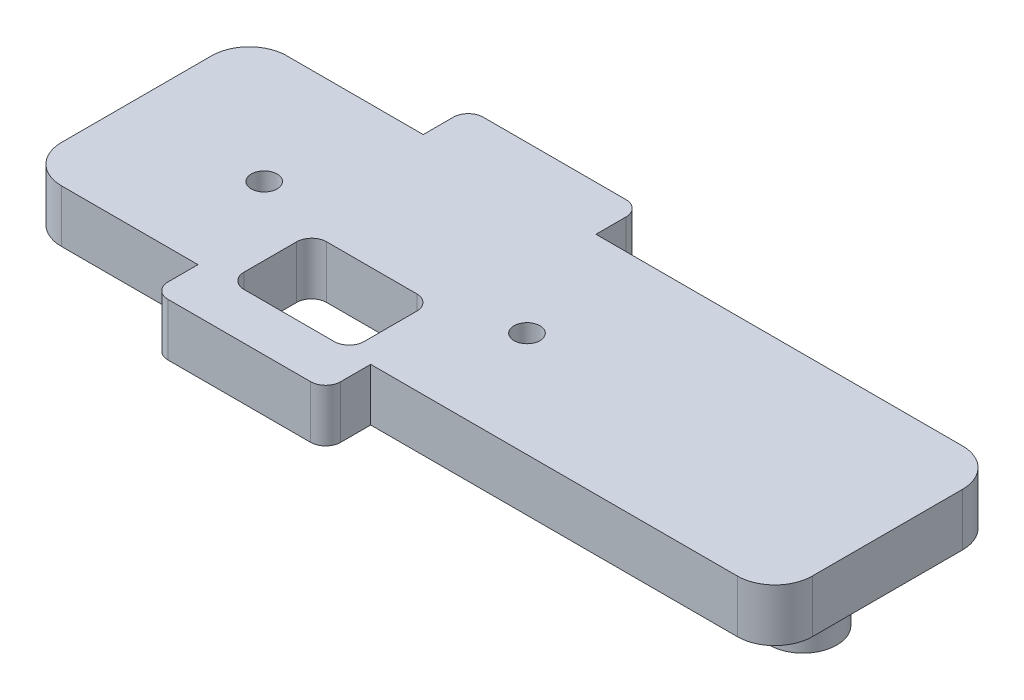
SolidWorks part; units mm, degrees
ref_plane "Front Plane" through (0, 0, 0) normal (0, 0, 1) x (1, 0, 0)
ref_plane "Top Plane" through (0, 0, 0) normal (0, 1, 0) x (1, 0, 0)
ref_plane "Right Plane" through (0, 0, 0) normal (1, 0, 0) x (0, 0, -1)
sketch "Sketch1" plane through (0, 0, 0) normal (0, 1, 0) x (1, 0, 0)
  line L1 (-45.1945, 17.8802) -> (54.8055, 17.8802)
  line L2 (-45.1945, 17.8802) -> (-45.1945, -12.1198)
  line L3 (-45.1945, -12.1198) -> (54.8055, -12.1198)
  line L4 (54.8055, 17.8802) -> (54.8055, -12.1198)
  dimension "D1" = 100
  dimension "D2" = 30
extrude "Boss-Extrude1" add sketch "Sketch1" along normal blind 7
ref_plane "Plane1" through (0, -1, 0) normal (0, -1, 0) x (-1, 0, 0)
sketch "Sketch2" plane through (0, -1, 0) normal (0, -1, 0) x (-1, 0, 0)
  line L0 (-54.8055, 2.8802) -> (57.5711, 2.8802) construction
  line L1 (-41.1646, -0.0198) -> (-44.5646, -0.0198)
  line L2 (-41.1646, -0.0198) -> (-41.1646, 5.7802)
  line L3 (-41.1646, 5.7802) -> (-44.5646, 5.7802)
  line L4 (-44.5646, -0.0198) -> (-44.5646, 5.7802)
  line L5 (-54.8055, -12.1198) -> (-54.8055, 17.8802) construction
  line L6 (-42.8646, -12.1198) -> (-42.8646, 27.765) construction
  line L8 (45.1945, -12.1198) -> (-54.8055, -12.1198) construction
  dimension "D1" = 3.4
  dimension "D2" = 5.8
  dimension "D3" = 1.7
  dimension "D4" = 2.9
extrude "Boss-Extrude2" add sketch "Sketch2" along normal blind 6 separate body
shell "Shell1" thickness 1 removed face at (42.8646, -7, -2.8802) outward yes
sketch "Sketch3" plane through (0, 0, 0) normal (0, -1, 0) x (-1, 0, 0)
  line L0 (-42.8646, -0.0198) -> (-42.8646, 11.0227) construction
  line L1 (-44.5646, -0.0198) -> (-41.1646, -0.0198) construction
  line L2 (-41.1646, 2.8802) -> (-49.8164, 2.8802) construction
  line L3 (-41.1646, -0.0198) -> (-41.1646, 5.7802) construction
  point P9 (-42.8646, 2.8802)
sketch "Sketch4" plane through (0, 0, 0) normal (0, -1, 0) x (-1, 0, 0)
  circle A0 centre (-42.9099, 3.5376) radius 4.5
  circle A1 centre (-42.9099, 3.5376) radius 3.7
  dimension "D1" = 7.4
extrude "Boss-Extrude3" add sketch "Sketch4" along normal blind 10
sketch "Sketch5" plane through (0, 0, 0) normal (0, -1, 0) x (-1, 0, 0)
  circle A0 centre (-42.8646, 2.8802) radius 4.25
  circle A1 centre (-42.8646, 2.8802) radius 5.5
extrude "Boss-Extrude4" add sketch "Sketch5" along normal blind 4
fillet "Fillet1" radius 5 4 edges at (-45.1945, 3.5, -17.8802) (-45.1945, 3.5, 12.1198) (54.8055, 3.5, -17.8802) (54.8055, 3.5, 12.1198)
sketch "Sketch6" plane through (0, 0, 0) normal (0, -1, 0) x (-1, 0, 0)
  line L0 (40.1945, -12.1198) -> (-49.8055, -12.1198) construction
  line L1 (22.0125, -12.1198) -> (-0.9875, -12.1198)
  line L2 (22.0125, -12.1198) -> (22.0125, -18.1198)
  line L3 (22.0125, -18.1198) -> (-0.9875, -18.1198)
  line L4 (-0.9875, -12.1198) -> (-0.9875, -18.1198)
  line L5 (45.1945, 2.8802) -> (44.2396, 2.8802) construction
  line L6 (45.1945, 12.8802) -> (45.1945, -7.1198) construction
  line L7 (22.0125, 23.8802) -> (-0.9875, 23.8802)
  line L8 (-0.9875, 17.8802) -> (-0.9875, 23.8802)
  line L9 (22.0125, 17.8802) -> (-0.9875, 17.8802)
  line L10 (22.0125, 17.8802) -> (22.0125, 23.8802)
  dimension "D1" = 6
  dimension "D2" = 23
extrude "Boss-Extrude5" add sketch "Sketch6" against normal up to surface (7 mm away) up to face at (4.8055, 7, -2.8802)
sketch "Sketch7" plane through (0, 0, 0) normal (0, -1, 0) x (-1, 0, 0)
  line L0 (40.1945, -12.1198) -> (22.0125, -12.1198) construction
  line L1 (-0.9875, -12.1198) -> (-49.8055, -12.1198) construction
  circle A0 centre (27.1973, 1.8802) radius 1.725
  circle A1 centre (-7.8027, 1.8802) radius 1.725
  dimension "D1" = 35
  dimension "D2" = 14
  dimension "D3" = 14
extrude "Cut-Extrude1" cut sketch "Sketch7" against normal up to surface (7 mm away) up to face at (-2.8535, 7, -2.8802)
fillet "Fillet2" radius 2 4 edges at (0.9875, 3.5, -23.8802) (-22.0125, 3.5, -23.8802) (0.9875, 3.5, 18.1198) (-22.0125, 3.5, 18.1198)
sketch "Sketch8" plane through (0, 0, 0) normal (0, -1, 0) x (-1, 0, 0)
  line L0 (1.0125, -18.1198) -> (20.0125, -18.1198) construction
  line L1 (18.0789, -11.9198) -> (2.0789, -11.9198)
  line L2 (18.0789, -11.9198) -> (18.0789, -0.9198)
  line L3 (18.0789, -0.9198) -> (2.0789, -0.9198)
  line L4 (2.0789, -11.9198) -> (2.0789, -0.9198)
  dimension "D1" = 16
  dimension "D2" = 11
  dimension "D3" = 6.2
extrude "Cut-Extrude2" cut sketch "Sketch8" against normal up to surface (7 mm away) up to face at (-27.1973, 7, -0.1552)
fillet "Fillet3" radius 2 4 edges at (-2.0789, 3.5, 0.9198) (-18.0789, 3.5, 0.9198) (-2.0789, 3.5, 11.9198) (-18.0789, 3.5, 11.9198)
